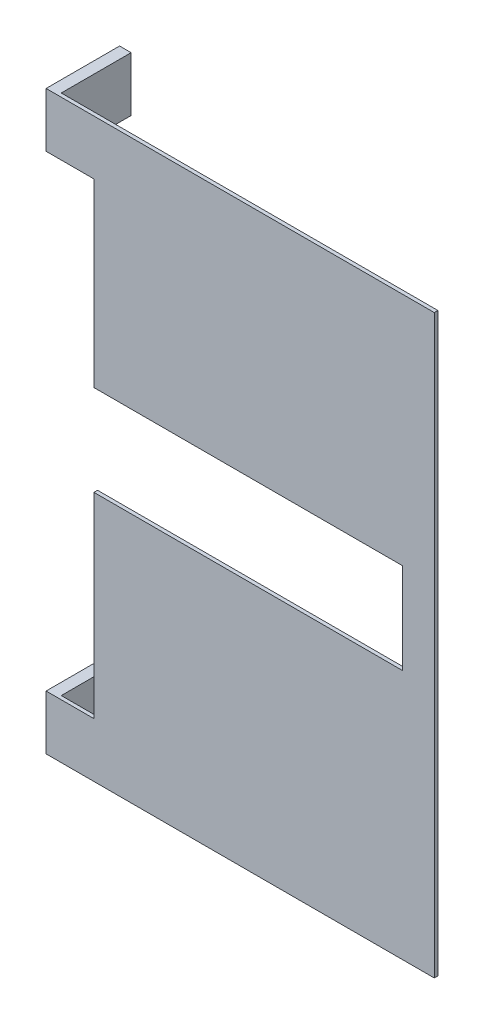
SolidWorks part; units mm, degrees
ref_plane "Front Plane" through (0, 0, 0) normal (0, 0, 1) x (1, 0, 0)
ref_plane "Top Plane" through (0, 0, 0) normal (0, 1, 0) x (1, 0, 0)
ref_plane "Right Plane" through (0, 0, 0) normal (1, 0, 0) x (0, 0, -1)
sketch "Sketch1" plane through (0, 0, 0) normal (0, 0, 1) x (1, 0, 0)
  line L0 (2.5917, 2.54) -> (2.5917, -124.46)
  line L7 (-72.4142, -124.46) -> (2.5917, -124.46)
  line L8 (2.5917, 2.54) -> (-72.4142, 2.54)
  line L9 (2.5917, 2.54) -> (-80.4142, 2.54) construction
  line L10 (-72.4142, 2.54) -> (-72.4142, -121.92)
  line L11 (2.5917, -121.92) -> (-80.4142, -121.92) construction
  line L12 (-72.4142, -121.92) -> (-72.4142, -124.46)
  dimension "D1" = 8
extrude "Boss-Extrude1" add sketch "Sketch1" along normal blind 0.8
sketch "Sketch2" plane through (0, 0, 0) normal (0, 0, 1) x (1, 0, 0)
  line L0 (-72.4142, 2.54) -> (-80.4142, 2.54)
  line L2 (-80.4142, -35.96) -> (-80.4142, 2.54) construction
  line L3 (-80.4142, -9.46) -> (-72.4142, -9.46)
  line L4 (-72.4142, 2.54) -> (-72.4142, -124.46) construction
  line L5 (-73.7163, -10.46) -> (-83.6842, -10.46) construction
  line L6 (-72.4142, -124.46) -> (-80.4142, -124.46)
  line L8 (-80.4142, -124.46) -> (-80.4142, -85.96) construction
  line L9 (-80.4142, -112.46) -> (-72.4142, -112.46)
  line L10 (-72.4142, -112.46) -> (-72.4142, -124.46)
  line L11 (-83.6842, -111.46) -> (-73.7163, -111.46) construction
  line L12 (-72.4142, 2.54) -> (-72.4142, -9.46)
  line L13 (-80.4142, 2.54) -> (-82.9542, 2.54)
  line L14 (-82.9542, 2.54) -> (-82.9542, -9.46)
  line L15 (-82.9542, -35.96) -> (-82.9542, 2.54) construction
  line L16 (-82.9542, -9.46) -> (-80.4142, -9.46)
  line L17 (-80.4142, -124.46) -> (-82.9542, -124.46)
  line L18 (-82.9542, -124.46) -> (-82.9542, -112.46)
  line L19 (-82.9542, -124.46) -> (-82.9542, -85.96) construction
  line L20 (-82.9542, -112.46) -> (-80.4142, -112.46)
  dimension "D1" = 1
  dimension "D2" = 1
extrude "Boss-Extrude2" add sketch "Sketch2" along normal blind 0.8
sketch "Sketch3" plane through (0, 0, 0) normal (0, 0, -1) x (-1, 0, 0)
  line L0 (82.9542, 2.54) -> (80.4142, 2.54)
  line L1 (80.4142, 2.54) -> (80.4142, 0) construction
  line L2 (-2.5917, 2.54) -> (82.9542, 2.54) construction
  line L3 (80.4142, 2.54) -> (80.4142, -9.46)
  line L4 (82.9542, -9.46) -> (72.4142, -9.46) construction
  line L5 (80.4142, -9.46) -> (82.9542, -9.46)
  line L6 (82.9542, -9.46) -> (82.9542, 2.54)
  line L7 (82.9542, -124.46) -> (80.4142, -124.46)
  line L8 (82.9542, -124.46) -> (-2.5917, -124.46) construction
  line L9 (80.4142, -121.92) -> (80.4142, -124.46) construction
  line L10 (80.4142, -124.46) -> (80.4142, -112.46)
  line L11 (72.4142, -112.46) -> (82.9542, -112.46) construction
  line L12 (80.4142, -112.46) -> (82.9542, -112.46)
  line L13 (82.9542, -112.46) -> (82.9542, -124.46)
extrude "Boss-Extrude3" add sketch "Sketch3" along normal up to surface (15.4 mm away) up to face at (2.5917, -60.96, 0.4)
sketch "Sketch4" plane through (0, 0, 0.8) normal (0, 0, 1) x (1, 0, 0)
  line L0 (-4.4142, -49.2778) -> (-72.4142, -49.2778)
  line L1 (-72.4142, -9.46) -> (-72.4142, -112.46) construction
  line L2 (-72.4142, -49.2778) -> (-72.4142, -69.2778)
  line L3 (-72.4142, -69.2778) -> (-4.4142, -69.2778)
  line L4 (-4.4142, -69.2778) -> (-4.4142, -49.2778)
  dimension "D1" = 68
  dimension "D2" = 20
extrude "Cut-Extrude1" cut sketch "Sketch4" against normal through all
